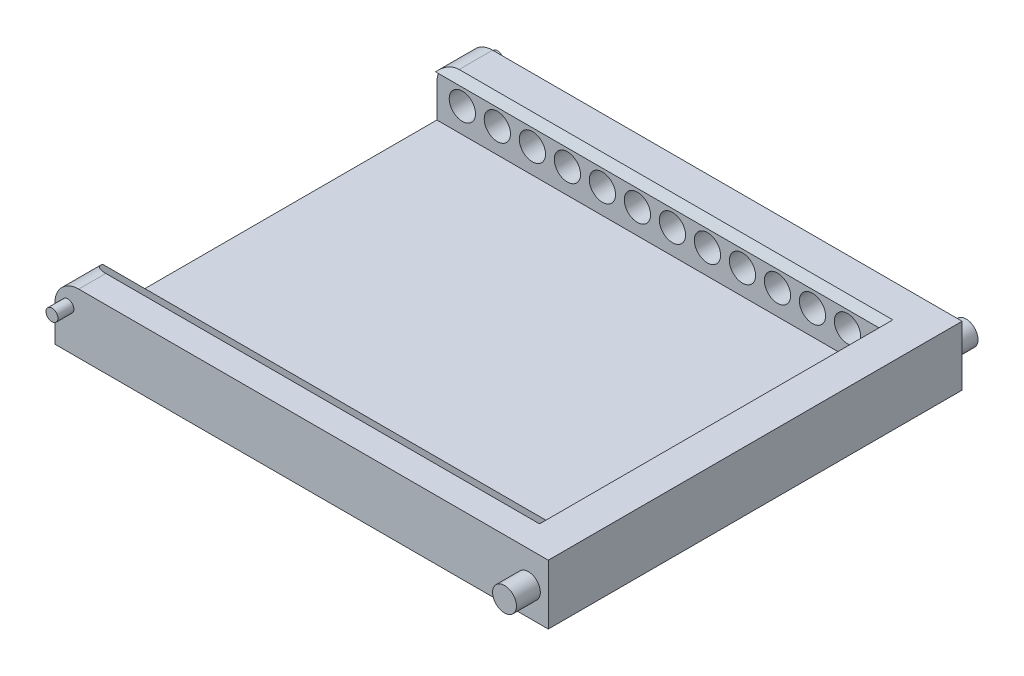
SolidWorks part; units mm, degrees
material "3003 Alloy"
ref_plane "Front Plane" through (0, 0, 0) normal (0, 0, 1) x (1, 0, 0)
ref_plane "Top Plane" through (0, 0, 0) normal (0, 1, 0) x (1, 0, 0)
ref_plane "Right Plane" through (0, 0, 0) normal (1, 0, 0) x (0, 0, -1)
sketch "Sketch1" plane through (0, 0, 0) normal (1, 0, 0) x (0, 0, -1)
  line L0 (-260, 0) -> (260, 0)
  line L1 (-220, 4) -> (220, 4)
  line L2 (0, 0) -> (0, 8) construction
  line L3 (-260, 0) -> (-260, 75)
  line L4 (-220, 4) -> (-220, 64)
  line L5 (220, 4) -> (220, 64)
  line L6 (260, 0) -> (260, 75)
  line L7 (-220, 64) -> (220, 64)
  line L8 (-260, 75) -> (260, 75)
  point P7 (0, 4)
  dimension "D1" = 520
  dimension "D2" = 440
  dimension "D3" = 4
  dimension "D4" = 75
  dimension "D5" = 60
extrude "Boss-Extrude1" add sketch "Sketch1" against normal blind 10
sketch "Sketch2" plane through (-10, 0, 0) normal (-1, 0, 0) x (0, 0, 1)
  line L0 (220, 64) -> (220, 4) construction
  line L1 (220, 4) -> (-220, 4) construction
  line L2 (-220, 64) -> (220, 64) construction
  line L3 (-220, 4) -> (-220, 64) construction
  line L4 (260, 0) -> (260, 75)
  line L5 (260, 75) -> (-260, 75)
  line L6 (-260, 75) -> (-260, 0)
  line L7 (-260, 0) -> (260, 0)
  line L8 (260, 0) -> (260, 75)
  line L9 (260, 75) -> (207, 75)
  line L10 (-260, 75) -> (-260, 0)
  line L11 (-260, 0) -> (260, 0)
  line L12 (220, 64) -> (220, 4)
  line L13 (220, 4) -> (-220, 4)
  line L14 (-220, 64) -> (-207, 64)
  line L15 (-220, 4) -> (-220, 64)
  line L16 (-207, 64) -> (-207, 75)
  line L17 (207, 64) -> (207, 75)
  line L18 (207, 64) -> (220, 64)
  line L19 (-207, 75) -> (-260, 75)
  dimension "D2" = 13
  dimension "D3" = 13
  dimension "D1" = 0
extrude "Boss-Extrude2" add sketch "Sketch2" along normal blind 575
sketch "Sketch3" plane through (0, 0, 0) normal (1, 0, 0) x (0, 0, -1)
  line L1 (-260, 75) -> (260, 75)
  line L2 (-260, 75) -> (-260, 0)
  line L3 (-260, 0) -> (260, 0)
  line L4 (260, 75) -> (260, 0)
extrude "Boss-Extrude3" add sketch "Sketch3" along normal blind 35
chamfer "Chamfer1" distance 19 angle 30 2 edges at (-297.5, 75, 207) (-297.5, 75, -207)
fillet "Fillet1" radius 30 2 edges at (-585, 75, 243) (-585, 75, -238.9848)
sketch "Sketch4" plane through (0, 0, 260) normal (0, 0, 1) x (1, 0, 0)
  line L0 (-585, 0) -> (-585, 45) construction
  line L2 (-555, 75) -> (35, 75) construction
  circle A0 centre (-568.68, 50) radius 7.5
  dimension "D1" = 15
  dimension "D2" = 16.32
  dimension "D3" = 25
extrude "Boss-Extrude4" add sketch "Sketch4" along normal blind 20
sketch "Sketch5" plane through (0, 0, -260) normal (0, 0, -1) x (-1, 0, 0)
  line L0 (585, 45) -> (585, 0) construction
  line L1 (555, 75) -> (-35, 75) construction
  circle A0 centre (568.68, 50) radius 7.5
  dimension "D1" = 15
  dimension "D2" = 16.32
  dimension "D3" = 25
extrude "Boss-Extrude5" add sketch "Sketch5" along normal blind 20
sketch "Sketch6" plane through (0, 0, 260) normal (0, 0, 1) x (1, 0, 0)
  line L0 (35, 75) -> (35, 0) construction
  line L1 (-585, 0) -> (35, 0) construction
  circle A0 centre (10, 35) radius 15
  dimension "D1" = 30
  dimension "D2" = 25
  dimension "D3" = 35
extrude "Boss-Extrude6" add sketch "Sketch6" along normal blind 30
sketch "Sketch7" plane through (0, 0, -260) normal (0, 0, -1) x (-1, 0, 0)
  line L0 (585, 0) -> (-35, 0) construction
  line L1 (-35, 0) -> (-35, 75) construction
  circle A0 centre (-10, 35) radius 15
  dimension "D1" = 30
  dimension "D2" = 35
  dimension "D3" = 25
extrude "Boss-Extrude7" add sketch "Sketch7" along normal blind 30
sketch "Sketch8" plane through (0, 0, 0) normal (0, 0, 1) x (1, 0, 0)
  line L0 (-585, 0) -> (35, 0) construction
  line L1 (35, 75) -> (35, 0) construction
  circle A0 centre (-25, 35) radius 16.5
  circle A1 centre (-69, 35) radius 16.5
  circle A2 centre (-113, 35) radius 16.5
  circle A3 centre (-157, 35) radius 16.5
  circle A4 centre (-201, 35) radius 16.5
  circle A5 centre (-245, 35) radius 16.5
  circle A6 centre (-289, 35) radius 16.5
  circle A7 centre (-333, 35) radius 16.5
  circle A8 centre (-377, 35) radius 16.5
  circle A9 centre (-421, 35) radius 16.5
  circle A10 centre (-465, 35) radius 16.5
  circle A11 centre (-509, 35) radius 16.5
  circle A12 centre (-553, 35) radius 16.5
  dimension "D1" = 33
  dimension "D2" = 35
  dimension "D3" = 60
  dimension "D4" = 13
extrude "Cut-Extrude1" cut sketch "Sketch8" against normal blind 250 and the other way blind 250
